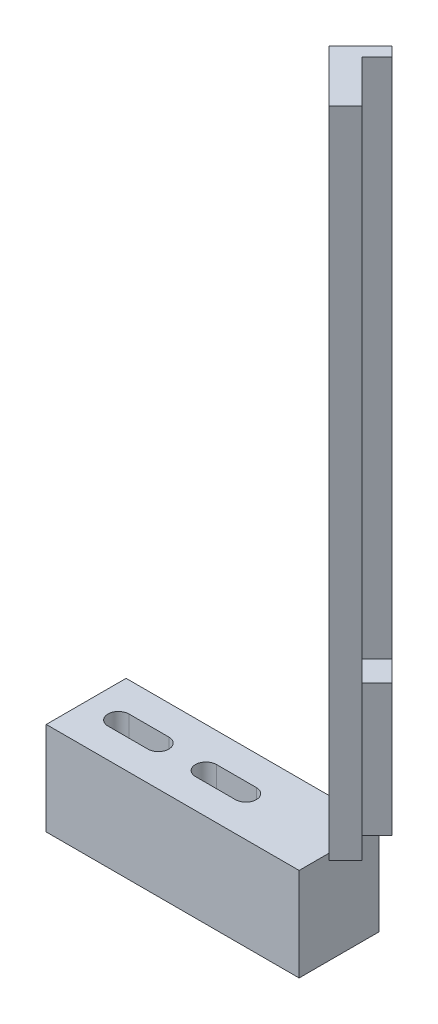
SolidWorks part; units mm, degrees
ref_plane "Front Plane" through (0, 0, 0) normal (0, 0, 1) x (1, 0, 0)
ref_plane "Top Plane" through (0, 0, 0) normal (0, 1, 0) x (1, 0, 0)
ref_plane "Right Plane" through (0, 0, 0) normal (1, 0, 0) x (0, 0, -1)
sketch "Sketch1" plane through (0, 0, 0) normal (0, 0, 1) x (1, 0, 0)
  line L0 (0, 0) -> (48.26, 0)
  line L6 (0, 0) -> (0, 17.78)
  line L10 (0, 17.78) -> (48.26, 17.78)
  line L11 (48.26, 0) -> (48.26, 17.78)
  dimension "D1" = 48.26
  dimension "D2" = 17.78
extrude "Boss-Extrude1" add sketch "Sketch1" against normal blind 15.24
sketch "Sketch3" plane through (0, 17.78, 0) normal (0, 1, 0) x (1, 0, 0)
  line L2 (48.4889, 11.7919) -> (51.3173, 14.6204)
  line L5 (51.3173, 14.6204) -> (47.3575, 18.5802)
  line L6 (39.5737, 14.3884) -> (40.4253, 15.24)
  line L10 (40.4253, 15.24) -> (45.5615, 20.3762)
  line L13 (48.26, 15.24) -> (0, 15.24) construction
  line L14 (45.5615, 20.3762) -> (47.3575, 18.5802)
  line L15 (47.3575, 18.5802) -> (44.5291, 15.7517)
  line L16 (49.5014, 4.4606) -> (52.6608, 7.62)
  line L17 (52.6608, 7.62) -> (44.5291, 15.7517)
  line L18 (39.5737, 14.3884) -> (49.5014, 4.4606)
  line M2 (48.26, 0) -> (48.26, 15.24)
  line M3 (48.26, 15.24) -> (0, 15.24)
  dimension "D1" = 2.54
  dimension "D2" = 7.2637
  dimension "D3" = 4.4681
  dimension "D4" = 5.6
  dimension "D5" = 11.5
  dimension "D6" = 1.2044
sketch "Sketch4" plane through (0, 17.78, 0) normal (0, 1, 0) x (1, 0, 0)
  line L0 (30.48, 7.62) -> (22.86, 7.62) construction
  line L1 (30.48, 5.62) -> (22.86, 5.62)
  line L2 (30.48, 9.62) -> (22.86, 9.62)
  line L3 (13.78, 7.62) -> (6.16, 7.62) construction
  line L4 (13.78, 5.62) -> (6.16, 5.62)
  line L5 (13.78, 9.62) -> (6.16, 9.62)
  line L6 (48.26, 0) -> (0, 0) construction
  line L7 (48.26, 15.24) -> (48.26, 0) construction
  arc A0 (30.48, 5.62) -> (30.48, 9.62) centre (30.48, 7.62) ccw
  arc A1 (22.86, 9.62) -> (22.86, 5.62) centre (22.86, 7.62) ccw
  arc A2 (13.78, 5.62) -> (13.78, 9.62) centre (13.78, 7.62) ccw
  arc A3 (6.16, 9.62) -> (6.16, 5.62) centre (6.16, 7.62) ccw
  point P2 (26.67, 7.62)
  point P7 (9.97, 7.62)
  point P14 (32.48, 7.62)
  point P16 (4.16, 7.62)
  point P18 (15.78, 7.62)
  point P19 (20.86, 7.62)
  dimension "D1" = 4
  dimension "D2" = 17.78
  dimension "D3" = 7.62
  dimension "D4" = 7.62
  dimension "D5" = 5.08
extrude "Cut-Extrude2" cut sketch "Sketch4" against normal through all
extrude "Boss-Extrude2" add sketch "Sketch3" along normal blind 124.72 contours L6 L18 L16 L17 M2 M3 | L16 L17 M2 | L17 L15 L14 L10 M3 region at (49.818, 17.78, -7.8931) region at (44.9059, 17.78, -11.7319) region at (44.2501, 17.78, -17.3573)
extrude "Boss-Extrude4" add sketch "Sketch3<7>" along normal blind 18.22
sketch "Sketch3<7>" plane through (0, 17.78, 0) normal (0, 1, 0) x (1, 0, 0) same geometry as "Sketch3"
extrude "Boss-Extrude5" add sketch "Sketch3<8>" along normal blind 25.22 contours L17 L2 L5 L15 M3 M2 | L17 L2 M2 M3 region at (48.1448, 17.78, -15.4927) region at (47.1869, 17.78, -14.1669)
sketch "Sketch3<8>" plane through (0, 17.78, 0) normal (0, 1, 0) x (1, 0, 0) same geometry as "Sketch3"
hole_wizard "Ø1.5mm Dowel Hole1" positions "Sketch6" profile "Sketch7" hole size "Ø1.5" standard "ANSI Metric" end condition through all
sketch "Sketch6" plane through (30.1404, 0, -30.1404) normal (0.7071, 0, -0.7071) x (-0.7071, 0, -0.7071)
  line L0 (-25.9487, 43) -> (-20.3487, 43) construction
  line L1 (-20.3487, 142.5) -> (-20.3487, 43) construction
  point P0 (-25.3487, 56.7)
  dimension "D1" = 13.7
  dimension "D2" = 5
sketch "Sketch7" plane through (48.0646, 56.7, -12.2162) normal (0, 1, 0) x (-0.7071, 0, -0.7071)
  line L0 (0, 0) -> (0, 42.625)
  line L1 (0, 42.625) -> (0.75, 42.625)
  line L2 (0.75, 42.625) -> (0.75, 0)
  line L5 (0.75, 0) -> (0, 0)
  line L11 (0, -6.35) -> (0, 107.95) construction
  dimension "Thru Hole Dia." = 1.5
  dimension "Thru Hole Depth" = 42.625
hole_wizard "Tapped Hole for M2.5x0.45 Helicoil1" positions "Sketch8" profile "Sketch9" tap size "M2.5x0.45" standard "Helicoil® Metric" end condition up to next
sketch "Sketch8" plane through (30.1404, 0, -30.1404) normal (0.7071, 0, -0.7071) x (-0.7071, 0, -0.7071)
  line L0 (-25.9487, 43) -> (-20.3487, 43) construction
  circle A0 centre (-25.3487, 56.7) radius 0.75 construction
  point P0 (-28.8987, 56.7)
  point P7 (-28.8987, 126.6998)
  point P10 (0, 0)
  dimension "D1" = 3.55
  dimension "D2" = 13.7
  dimension "D3" = 69.9999
sketch "Sketch9" plane through (50.5749, 56.7, -9.706) normal (0, 1, 0) x (-0.7071, 0, -0.7071)
  line L0 (0, 0) -> (0, 4.4681)
  line L1 (0, 4.4681) -> (1.275, 4.4681)
  line L2 (1.275, 4.4681) -> (1.275, 0)
  line L5 (1.275, 0) -> (0, 0)
  line L11 (0, -6.35) -> (0, 107.95) construction
  dimension "Thru Tap Drill Dia." = 2.55
  dimension "Thru Tap Drill Depth" = 4.4681
cosmetic thread "Hole Thread1" parameters "D1"=3.7998, "D2"=3.145
cosmetic thread "Hole Thread2" parameters "D1"=3.7998, "D2"=3.145
sketch "Sketch10" plane through (26.981, 0, -26.981) normal (-0.7071, 0, 0.7071) x (0.7071, 0, 0.7071)
  line L0 (25.3487, 127.2) -> (25.3487, 126.2) construction
  line L1 (26.0987, 127.2) -> (26.0987, 126.2)
  line L2 (24.5987, 127.2) -> (24.5987, 126.2)
  line L3 (25.9487, 43) -> (20.3487, 43) construction
  arc A0 (26.0987, 127.2) -> (24.5987, 127.2) centre (25.3487, 127.2) ccw
  arc A1 (24.5987, 126.2) -> (26.0987, 126.2) centre (25.3487, 126.2) ccw
  circle A2 centre (28.8987, 126.6998) radius 1.275 construction
  point P2 (25.3487, 126.7)
  point P7 (0, 0)
  point P8 (0, 0)
  dimension "D1" = 1
  dimension "D2" = 0.75
  dimension "D4" = 83.2
  dimension "D3" = 2.8
